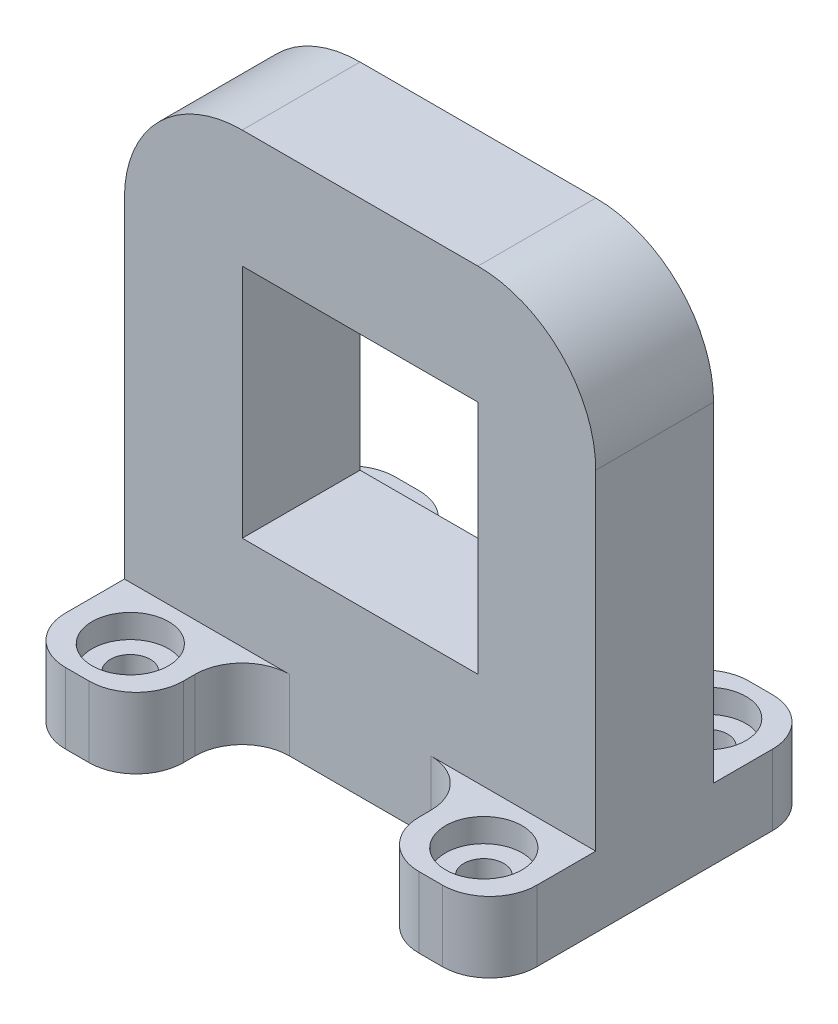
SolidWorks part; units mm, degrees
ref_plane "Plan de face" through (0, 0, 0) normal (0, 0, 1) x (1, 0, 0)
ref_plane "Plan de dessus" through (0, 0, 0) normal (0, 1, 0) x (1, 0, 0)
ref_plane "Plan de droite" through (0, 0, 0) normal (1, 0, 0) x (0, 0, -1)
sketch "Esquisse1" plane through (0, 0, 0) normal (0, 0, 1) x (1, 0, 0)
  line L0 (0, 0) -> (40, 0)
  line L1 (0, 0) -> (40, 0) construction
  line L2 (0, 0) -> (0, 44) construction
  line L3 (0, 44) -> (40, 44) construction
  line L4 (40, 0) -> (40, 44) construction
  line L5 (40, 0) -> (40, 44)
  line L6 (40, 44) -> (0, 44)
  line L7 (0, 44) -> (0, 0)
  line L9 (10, 34) -> (30, 34)
  line L10 (10, 34) -> (10, 14)
  line L11 (10, 14) -> (30, 14)
  line L12 (30, 34) -> (30, 14)
  dimension "D1" = 40
  dimension "D2" = 44
  dimension "D3" = 10
  dimension "D4" = 10
  dimension "D5" = 10
  dimension "D6" = 14
extrude "Boss.-Extru.1" add sketch "Esquisse1" along normal blind 10
sketch "Esquisse3" plane through (0, 0, 10) normal (0, 0, 1) x (1, 0, 0)
  line L0 (30, 0) -> (40, 0)
  line L3 (0, 6) -> (10, 6)
  line L4 (0, 44) -> (0, 0)
  line L5 (0, 0) -> (40, 0)
  line L6 (40, 0) -> (40, 44)
  line L7 (40, 44) -> (0, 44)
  line L8 (0, 6) -> (0, 0)
  line L9 (0, 0) -> (10, 0)
  line L12 (10, 0) -> (10, 6)
  line L14 (40, 0) -> (40, 6)
  line L15 (40, 6) -> (30, 6)
  line L16 (30, 0) -> (30, 6)
  line L17 (0, 0) -> (40, 0) construction
  dimension "D4" = 10
  dimension "D2" = 10
  dimension "D3" = 6
  dimension "D5" = 6
extrude "Boss.-Extru.2" add sketch "Esquisse3" along normal blind 9
sketch "Esquisse4" plane through (0, 6, 0) normal (0, 1, 0) x (1, 0, 0)
  line L0 (0, -19) -> (0, -10) construction
  line L1 (10, -10) -> (0, -10) construction
  line L2 (40, -19) -> (40, -10) construction
  line L3 (40, -10) -> (0, -10) construction
  circle A0 centre (5, -14.5) radius 1.5
  circle A1 centre (35, -14.5) radius 1.5
  dimension "D3" = 3
  dimension "D4" = 3
  dimension "D1" = 5
  dimension "D2" = 4.5
  dimension "D5" = 5
  dimension "D6" = 4.5
hole_wizard "Chambrage pour tête cylindrique fendue M31" positions "Esquisse5" profile "Esquisse6" counterbore size "M3" standard "ISO" end condition through all
sketch "Esquisse5" plane through (0, 6, 0) normal (0, 1, 0) x (1, 0, 0)
  point P0 (5, -14.5)
  point P3 (35, -14.5)
sketch "Esquisse6" plane through (5, 6, 14.5) normal (1, 0, 0) x (0, 0, 1)
  line L0 (0, 0) -> (0, 6)
  line L1 (0, 6) -> (1.7, 6)
  line L3 (1.7, 6) -> (1.7, 2)
  line L4 (1.7, 2) -> (3.25, 2)
  line L5 (3.25, 2) -> (3.25, 0)
  line L7 (3.25, 0) -> (0, 0)
  line L11 (0, -6.35) -> (0, 107.95) construction
  dimension "Diamètre du perçage jusqu'au prochain" = 3.4
  dimension "Profondeur du perçage jusqu'au prochain" = 6
  dimension "Diamètre du chambrage" = 6.5
  dimension "Profondeur du chambrage" = 2
ref_plane "Plan1" through (0, 0, 5) normal (0, 0, 1) x (1, 0, 0)
mirror "Symétrie1" about plane through (0, 0, 5) normal (0, 0, 1) of "Chambrage pour tête cylindrique fendue M31", "Boss.-Extru.2"
fillet "Congé1" radius 4 12 edges at (40, 3, 19) (30, 3, 19) (0, 3, 19) (10, 3, 19) (30, 3, 10) (10, 3, 10) (0, 3, -9) (10, 3, -9) (10, 3, 0) (30, 3, 0) (30, 3, -9) (40, 3, -9)
fillet "Congé2" radius 10 2 edges at (0, 44, 5) (40, 44, 5)
equation "\"largeur_cremail\"= 20"
equation "\"hauteur_cremail\"= 20"
equation "\"epaiss_cadre\"= 10"
equation "\"hauteur_basecremail_sol\"= 4"
equation "\"D1@Esquisse1\"=\"largeur_cremail\"+\"epaiss_cadre\"*2"
equation "\"D2@Esquisse1\"=\"hauteur_basecremail_sol\"+\"hauteur_cremail\"+\"epaiss_cadre\"*2"
equation "\"D3@Esquisse1\"=\"epaiss_cadre\""
equation "\"D4@Esquisse1\"=\"epaiss_cadre\""
equation "\"D5@Esquisse1\"=\"epaiss_cadre\""
equation "\"D6@Esquisse1\"=\"hauteur_basecremail_sol\"+\"epaiss_cadre\""
equation "\"D1@Boss.-Extru.1\"=\"epaiss_cadre\""
equation "\"D2@Esquisse3\"=\"epaiss_cadre\""
equation "\"D4@Esquisse3\"=\"epaiss_cadre\""
equation "\"D5@Esquisse3\"=\"D3@Esquisse3\""
equation "\"D1@Esquisse4\"=\"epaiss_cadre\"/2"
equation "\"D5@Esquisse4\"=\"epaiss_cadre\"/2"
equation "\"D6@Esquisse4\"=4.5"
